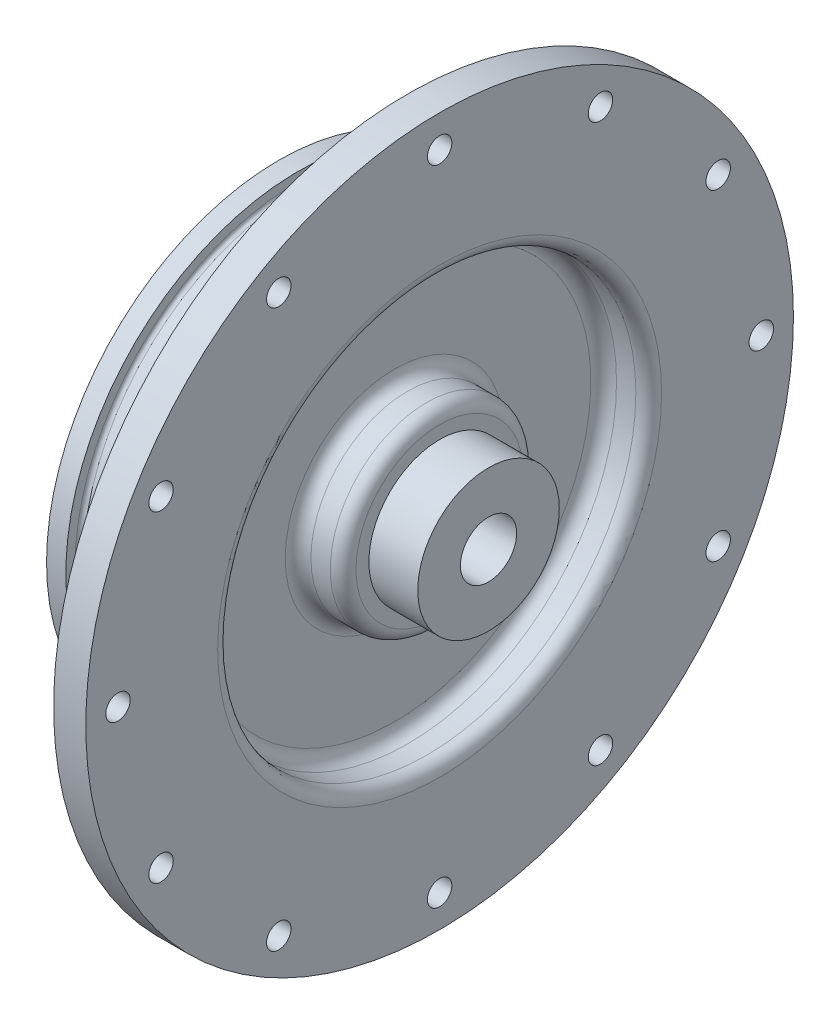
SolidWorks part; units mm, degrees
material "7075-T6 (SN)"
ref_plane "Front Plane" through (0, 0, 0) normal (0, 0, 1) x (1, 0, 0)
ref_plane "Top Plane" through (0, 0, 0) normal (0, 1, 0) x (1, 0, 0)
ref_plane "Right Plane" through (0, 0, 0) normal (1, 0, 0) x (0, 0, -1)
sketch "Sketch1" plane through (0, 0, 0) normal (1, 0, 0) x (0, 0, -1)
  circle A0 centre (0, 0) radius 69.85
  dimension "D1" = 139.7
extrude "Boss-Extrude1" add sketch "Sketch1" along normal blind 6.35
sketch "Sketch2" plane through (0, 0, 0) normal (-1, 0, 0) x (0, 0, 1)
  circle A0 centre (0, 0) radius 45.847
  dimension "D1" = 91.694
extrude "Boss-Extrude2" add sketch "Sketch2" along normal blind 25.4
sketch "Sketch10" plane through (0, 0, 0) normal (0, 1, 0) x (1, 0, 0)
  line L0 (0, 0) -> (-53.2238, 0) construction
  line L1 (-26.2636, 0) -> (26.2636, 0) construction
  line L2 (0, 0) -> (0, 64.5447) construction
  line L3 (0, -62.865) -> (0, 62.865) construction
ref_plane "Plane1" through (0, 0, -45.847) normal (0, 0, -1) x (-1, 0, 0)
sketch "Sketch11" plane through (0, 0, -45.847) normal (0, 0, -1) x (-1, 0, 0)
  line L0 (0, 0) -> (53.2238, 0) construction
  line L1 (0, -45.847) -> (0, 45.847) construction
  circle A0 centre (7.62, 0) radius 1.8986
  dimension "D2" = 3.7973
  dimension "D1" = 7.62
extrude "Cut-Extrude3" cut sketch "Sketch11" against normal blind 10.16
pattern_circular "CirPattern1" count 12 over 360 about axis through (0, 0, 0) along (-1, 0, 0) of "Cut-Extrude3" reverse direction yes
sketch "Sketch15" plane through (6.35, 0, 0) normal (1, 0, 0) x (0, 0, -1)
  circle A0 centre (0, 0) radius 5.5562
  dimension "D1" = 11.1125
extrude "Cut-Extrude4" cut sketch "Sketch15" against normal through all both and the other way through all
sketch "Sketch16" plane through (0, 0, 0) normal (0, 0, 1) x (1, 0, 0)
  line L0 (-9.5186, 45.847) -> (-25.4, 45.847) construction
  line L1 (-21.59, 45.847) -> (-14.4018, 45.847)
  line L2 (-21.59, 45.847) -> (-21.59, 44.069)
  line L3 (-20.828, 43.307) -> (-15.1638, 43.307)
  line L4 (-14.4018, 45.847) -> (-14.4018, 44.069)
  line L5 (0, 0) -> (-53.2238, 0) construction
  line L6 (-25.4, 45.847) -> (-25.4, -45.847) construction
  arc A0 (-14.4018, 44.069) -> (-15.1638, 43.307) centre (-15.1638, 44.069) cw
  arc A1 (-20.828, 43.307) -> (-21.59, 44.069) centre (-20.828, 44.069) cw
  point P8 (-26.6119, 0)
  point P13 (-14.4018, 43.307)
  point P16 (-21.59, 43.307)
  dimension "D4" = 0.762
  dimension "D1" = 43.307
  dimension "D2" = 3.81
  dimension "D3" = 7.1882
revolve "Cut-Revolve1" cut sketch "Sketch16" angle 360 about L0
sketch "Sketch17" plane through (6.35, 0, 0) normal (1, 0, 0) x (0, 0, -1)
  circle A0 centre (0, 0) radius 13.97
  circle A1 centre (0, 0) radius 5.5562
  dimension "D1" = 27.94
  dimension "D2" = 11.1125
extrude "Boss-Extrude3" add sketch "Sketch17" along normal blind 9.652
cosmetic thread "Cosmetic Thread1" parameters "D2"=23.1953
sketch "Sketch18" plane through (0, 0, 0) normal (0, 0, 1) x (1, 0, 0)
  line L0 (6.35, -69.85) -> (6.35, 69.85) construction
  line L1 (6.35, 41.275) -> (-2.54, 41.275)
  line L2 (6.35, 41.275) -> (6.35, 19.05)
  line L3 (6.35, 19.05) -> (-2.54, 19.05)
  line L4 (-2.54, 41.275) -> (-2.54, 19.05)
  line L5 (0, 0) -> (-53.2238, 0) construction
  dimension "D1" = 8.89
  dimension "D2" = 19.05
  dimension "D3" = 41.275
revolve "Cut-Revolve2" cut sketch "Sketch18" angle 360 about L0
fillet "Fillet1" radius 2.54 4 edges at (6.35, 0, -41.275) (-2.54, 0, -41.275) (-2.54, 0, -19.05) (6.35, 0, -19.05)
sketch "Sketch19" plane through (6.35, 0, 0) normal (1, 0, 0) x (0, 0, -1)
  line L0 (0, 0) -> (0, 63.5) construction
  circle A0 centre (0, 0) radius 57.15 construction
  circle A1 centre (0, 0) radius 63.5 construction
  circle A2 centre (0, 63.5) radius 2.413
  circle A3 centre (31.75, 54.9926) radius 2.413
  circle A4 centre (54.9926, 31.75) radius 2.413
  circle A5 centre (63.5, 0) radius 2.413
  circle A6 centre (54.9926, -31.75) radius 2.413
  circle A7 centre (31.75, -54.9926) radius 2.413
  circle A8 centre (0, -63.5) radius 2.413
  circle A9 centre (-31.75, -54.9926) radius 2.413
  circle A10 centre (-54.9926, -31.75) radius 2.413
  circle A11 centre (-63.5, 0) radius 2.413
  circle A12 centre (-54.9926, 31.75) radius 2.413
  circle A13 centre (-31.75, 54.9926) radius 2.413
  point P30 (0, 0)
  dimension "D1" = 114.3
  dimension "D2" = 127
  dimension "D3" = 4.826
  dimension "D4" = 12
extrude "Cut-Extrude5" cut sketch "Sketch19" against normal through all
